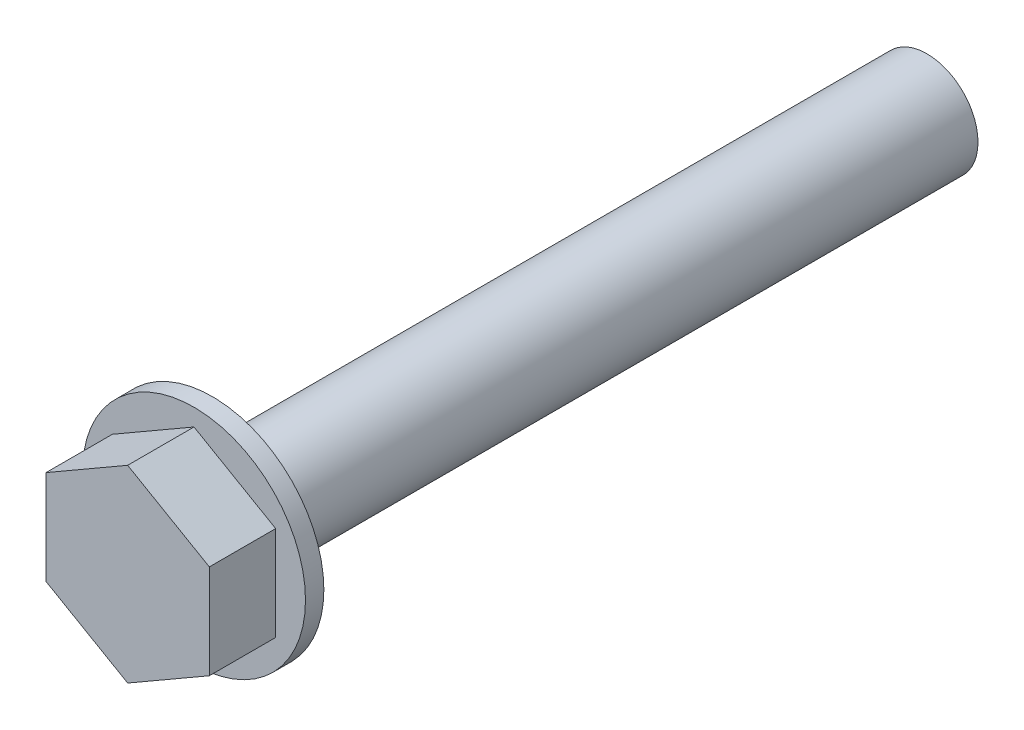
SolidWorks part; units mm, degrees
material "AISI Type 316L stainless steel"
ref_plane "Front Plane" through (0, 0, 0) normal (0, 0, 1) x (1, 0, 0)
ref_plane "Top Plane" through (0, 0, 0) normal (0, 1, 0) x (1, 0, 0)
ref_plane "Right Plane" through (0, 0, 0) normal (1, 0, 0) x (0, 0, -1)
sketch "Extrude sketch 1" plane through (0, 0, 0) normal (0, 0, 1) x (1, 0, 0)
  circle A0 centre (0, 0) radius 10.92
  dimension "D1" = 21.84
extrude "Extrude 1" add sketch "Extrude sketch 1" along normal blind 1.8 separate body
sketch "Extrude sketch 2" plane through (0, 0, 0) normal (0, 0, 1) x (1, 0, 0)
  line L0 (8, 4.6188) -> (0, 9.2376)
  line L1 (0, 9.2376) -> (-8, 4.6188)
  line L2 (-8, 4.6188) -> (-8, -4.6188)
  line L3 (-8, -4.6188) -> (0, -9.2376)
  line L4 (0, -9.2376) -> (8, -4.6188)
  line L5 (8, -4.6188) -> (8, 4.6188)
  dimension "D1" = 8
  dimension "D2" = 4.6188
extrude "Extrude 2" add sketch "Extrude sketch 2" along normal blind 6.5 from offset 1.8 separate body
sketch "Extrude sketch 3" plane through (0, 0, 0) normal (0, 0, 1) x (1, 0, 0)
  circle A0 centre (0, 0) radius 5
  dimension "D1" = 10
extrude "Extrude 3" add sketch "Extrude sketch 3" along normal blind 70.01 from offset 70 separate body offset against normal yes
combine bodies "Combine (weld / assembly of features)" operation type add bodies to combine 101 103 102
